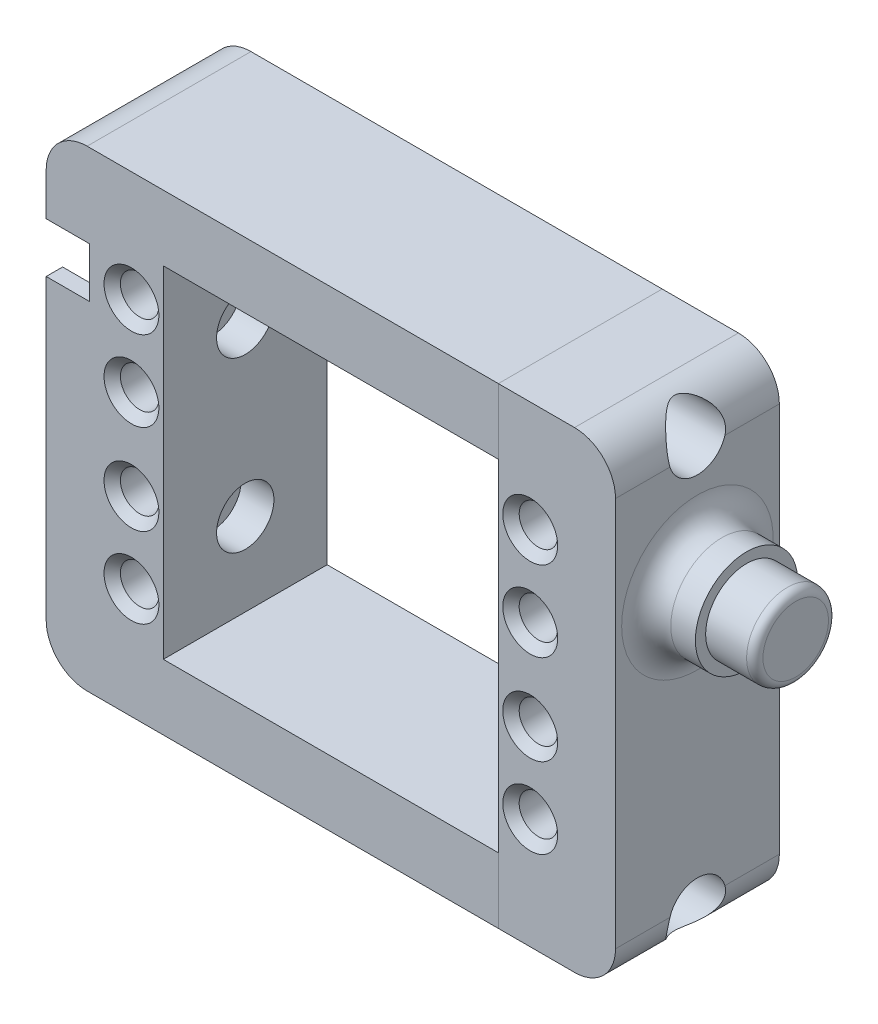
SolidWorks part; units mm, degrees
material "ABS"
ref_plane "Front Plane" through (0, 0, 0) normal (0, 0, 1) x (1, 0, 0)
ref_plane "Top Plane" through (0, 0, 0) normal (0, 1, 0) x (1, 0, 0)
ref_plane "Right Plane" through (0, 0, 0) normal (1, 0, 0) x (0, 0, -1)
sketch "Sketch1" plane through (0, 0, 0) normal (1, 0, 0) x (0, 0, -1)
  line L1 (-10, 10) -> (10, 10)
  line L2 (-10, 10) -> (-10, -10)
  line L3 (-10, -10) -> (10, -10)
  line L4 (10, 10) -> (10, -10)
  line L5 (-10, 10) -> (10, -10) construction
  line L6 (-10, -10) -> (10, 10) construction
  point P0 (0, 0)
  dimension "D1" = 20
  dimension "D2" = 20
extrude "Boss-Extrude1" add sketch "Sketch1" along normal blind 20
sketch "Sketch2" plane through (20, 0, 0) normal (1, 0, 0) x (0, 0, -1)
  line L1 (-10, 35) -> (10, 35)
  line L2 (-10, 35) -> (-10, -35)
  line L3 (-10, -35) -> (10, -35)
  line L4 (10, 35) -> (10, -35)
  line L5 (-10, 35) -> (10, -35) construction
  line L6 (-10, -35) -> (10, 35) construction
  point P0 (0, 0)
  dimension "D1" = 20
  dimension "D2" = 70
extrude "Boss-Extrude2" add sketch "Sketch2" along normal blind 10.3
sketch "Sketch4" plane through (30.3, 0, 0) normal (1, 0, 0) x (0, 0, -1)
  line L0 (0, 7.65) -> (0, 8.1702) construction
  line L1 (7.65, 7.65) -> (-7.65, 7.65) construction
  line L17 (4.15, -26.55) -> (-4.15, -26.55) construction
  line L18 (-7.65, 7.65) -> (7.65, 7.65) construction
  line L22 (-7.65, 7.65) -> (-7.65, -27.55) construction
  line L23 (-7.65, -27.55) -> (7.65, -27.55) construction
  line L24 (7.65, 7.65) -> (7.65, -27.55) construction
  line L25 (-7.65, 7.65) -> (7.65, -27.55) construction
  line L26 (-7.65, -27.55) -> (7.65, 7.65) construction
  line L27 (4.15, -26.55) -> (4.15, -28.55) construction
  line L28 (4.15, -28.55) -> (-4.15, -28.55) construction
  line L29 (-4.15, -26.55) -> (-4.15, -28.55) construction
  line L30 (4.15, -26.55) -> (-4.15, -28.55) construction
  line L31 (4.15, -28.55) -> (-4.15, -26.55) construction
  line L34 (4.15, -28.55) -> (-4.15, -28.55)
  line L35 (-4.15, -28.55) -> (-4.15, -7.3118)
  line L36 (4.15, -28.55) -> (4.15, -7.3118)
  arc A1 (4.15, -6.4265) -> (-4.15, -6.4265) centre (0, 0) ccw construction
  arc A2 (4.15, -7.3118) -> (-4.15, -7.3118) centre (0, 0) ccw
  point P1 (0, -27.55)
  point P7 (0, -13.75)
  point P10 (0, 7.65)
  point P14 (0, -9.95)
  dimension "D1" = 15.3
  dimension "D5" = 2
  dimension "D2" = 15.3
  dimension "D3" = 35.2
  dimension "D4" = 8.3
extrude "Cut-Extrude1" cut sketch "Sketch4" against normal blind 5.8
fillet "Fillet1" radius 4.15 2 edges at (27.4, -28.55, 4.15) (27.4, -28.55, -4.15)
fillet "Fillet2" radius 10 2 edges at (27.4, -7.3118, 4.15) (27.4, -7.3118, -4.15)
sketch "Sketch5" plane through (0, 0, 0) normal (-1, 0, 0) x (0, 0, 1)
  circle A0 centre (0, 0) radius 1.75
  dimension "D1" = 3.5
extrude "Cut-Extrude2" cut sketch "Sketch5" against normal through all
sketch "Sketch6" plane through (24.5, 0, 0) normal (1, 0, 0) x (0, 0, -1)
  line L0 (0, -19.35) -> (0, 0) construction
  line L1 (0, -25.65) -> (0, -23.15) construction
  line L2 (0, -23.15) -> (0, -21.85) construction
  line L3 (0, -21.85) -> (0, -19.35) construction
  line L5 (0, 0) -> (1.164, 0) construction
  line L6 (0, 0) -> (0, -9.35) construction
  line L7 (0, -9.35) -> (1.164, -9.35) construction
  line L8 (1.164, 0) -> (1.164, -9.35) construction
  line L9 (0, 0) -> (1.164, -9.35) construction
  line L10 (0, -9.35) -> (1.164, 0) construction
  circle A0 centre (0, -20.6) radius 1.75
  circle A1 centre (0, -9.35) radius 1.75 construction
  point P11 (0.582, -4.675)
  dimension "D5" = 3.5
  dimension "D6" = 9.35
  dimension "D7" = 3.5
  dimension "D1" = 19.35
  dimension "D2" = 2.5
  dimension "D3" = 1.3
  dimension "D4" = 2.5
extrude "Cut-Extrude3" cut sketch "Sketch6" against normal up to next
sketch "Sketch13" plane through (0, 0, 0) normal (-1, 0, 0) x (0, 0, 1)
  line L1 (-10, 10) -> (10, 10)
  line L2 (-10, 10) -> (-10, -10)
  line L3 (-10, -10) -> (10, -10)
  line L4 (10, 10) -> (10, -10)
extrude "Cut-Extrude9" cut sketch "Sketch13" against normal up to surface (20 mm away) up to face at (20, 22.5, 0)
sketch "Sketch29" plane through (30.3, 0, 0) normal (1, 0, 0) x (0, 0, -1)
  line L0 (0, 0) -> (0, 2.6) construction
  line L1 (15.1094, -8.7) -> (15.1094, -2.6)
  line L2 (0, 2.6) -> (-15.1094, 2.6)
  line L4 (0, 2.6) -> (0, 3.8)
  line L5 (0, 3.8) -> (0, 7.5)
  line L6 (0, 7.5) -> (0, 8.7)
  line L7 (0, 8.7) -> (-15.1094, 8.7)
  line L8 (-15.1094, 8.7) -> (-15.1094, 2.6)
  line L9 (0, -2.6) -> (15.1094, -2.6)
  line L10 (0, -2.6) -> (0, -3.8)
  line L11 (0, -3.8) -> (0, -7.5)
  line L12 (0, -7.5) -> (0, -8.7)
  line L13 (0, -8.7) -> (15.1094, -8.7)
  point P19 (0, 0)
  dimension "D1" = 2.6
  dimension "D2" = 1.2
  dimension "D3" = 3.7
  dimension "D4" = 1.2
  dimension "D5" = 2
extrude "Cut-Extrude18" cut sketch "Sketch29" against normal blind 5.3
sketch "Sketch32" plane through (30.3, 0, 0) normal (1, 0, 0) x (0, 0, -1)
  line L0 (0, -28.55) -> (0, -38.725) construction
  line L1 (10, -35) -> (10, -8.7) construction
  line L2 (-10, -35) -> (10, -35)
  line L3 (-10, -35) -> (-10, -38.725)
  line L4 (-10, -38.725) -> (10, -38.725)
  line L5 (10, -35) -> (10, -38.725)
  dimension "D1" = 10.175
extrude "Boss-Extrude3" add sketch "Sketch32" against normal up to surface (10.3 mm away) up to face at (20, 0, 0)
sketch "Sketch31" plane through (30.3, 0, 0) normal (1, 0, 0) x (0, 0, -1)
  line L2 (0, 8.7) -> (0, 18.875) construction
  line L3 (10, -2.6) -> (10, 35) construction
  line L4 (-10, 35) -> (10, 35)
  line L5 (-10, 35) -> (-10, 18.875)
  line L6 (-10, 18.875) -> (10, 18.875)
  line L7 (10, 35) -> (10, 18.875)
  dimension "D1" = 10.175
extrude "Cut-Extrude19" cut sketch "Sketch31" against normal through all
sketch "Sketch34" plane through (20, 0, 0) normal (-1, 0, 0) x (0, 0, 1)
  line L4 (10, -38.725) -> (10, 18.875)
  line L5 (10, 18.875) -> (-10, 18.875)
  line L6 (-10, 18.875) -> (-10, -38.725)
  line L7 (-10, -38.725) -> (10, -38.725)
  line L8 (10, -38.725) -> (10, 18.875)
  line L9 (10, 18.875) -> (-10, 18.875)
  line L10 (-10, 18.875) -> (-10, -38.725)
  line L11 (-10, -38.725) -> (10, -38.725)
  circle A0 centre (0, -20.6) radius 1.75 construction
  circle A1 centre (0, 0) radius 1.75 construction
  circle A2 centre (0, -20.6) radius 1.75
  circle A3 centre (0, 0) radius 1.75
  dimension "D1" = 0
extrude "Boss-Extrude5" add sketch "Sketch34" along normal blind 4
sketch "Sketch35" plane through (16, 0, 0) normal (-1, 0, 0) x (0, 0, 1)
  line L0 (10, -38.725) -> (10, 18.875) construction
  line L1 (-10, 18.875) -> (10, 18.875)
  line L2 (-10, 18.875) -> (-10, 10.875)
  line L3 (-10, 10.875) -> (10, 10.875)
  line L4 (10, 18.875) -> (10, 10.875)
  line L5 (0, 10.875) -> (0, -30.725) construction
  line L6 (-10, -38.725) -> (10, -38.725)
  line L7 (-10, -38.725) -> (-10, -30.725)
  line L8 (-10, -30.725) -> (10, -30.725)
  line L9 (10, -38.725) -> (10, -30.725)
  dimension "D1" = 41.6
extrude "Boss-Extrude6" add sketch "Sketch35" along normal blind 40.9
sketch "Sketch37" plane through (-24.9, 0, 0) normal (-1, 0, 0) x (0, 0, 1)
  line L1 (-10, 18.875) -> (10, 18.875)
  line L2 (-10, 18.875) -> (-10, -38.725)
  line L3 (-10, -38.725) -> (10, -38.725)
  line L4 (10, 18.875) -> (10, -38.725)
extrude "Boss-Extrude7" add sketch "Sketch37" along normal blind 14.3
sketch "Sketch38" plane through (0, 0, 10) normal (0, 0, 1) x (1, 0, 0)
  line L0 (-24.9, 10.875) -> (-24.9, -9.925) construction
  line L1 (-24.9, -9.925) -> (-24.9, -30.725) construction
  line L2 (-24.9, -30.725) -> (-24.9, 10.875) construction
  line L3 (-24.9, -9.925) -> (-39.2, -9.925) construction
  line L4 (-39.2, -38.725) -> (-39.2, 18.875) construction
  line L5 (-24.9, 0.475) -> (-28.79, 0.475) construction
  line L6 (-28.79, 0.475) -> (-28.79, 5.375) construction
  line L7 (-24.9, 10.875) -> (16, 10.875) construction
  line L8 (-4.45, 10.875) -> (-4.45, -38.725) construction
  line L9 (-39.2, -38.725) -> (30.3, -38.725) construction
  circle A0 centre (-28.79, 5.375) radius 2.35
  circle A1 centre (-28.79, -4.425) radius 2.35
  circle A2 centre (-28.79, -25.225) radius 2.35
  circle A3 centre (-28.79, -15.425) radius 2.35
  circle A4 centre (19.89, 5.375) radius 2.35
  circle A5 centre (19.89, -4.425) radius 2.35
  circle A6 centre (19.89, -15.425) radius 2.35
  circle A7 centre (19.89, -25.225) radius 2.35
  dimension "D4" = 4.7
  dimension "D1" = 41.6
  dimension "D2" = 3.89
  dimension "D3" = 4.9
extrude "Cut-Extrude20" cut sketch "Sketch38" against normal blind 8
chamfer "Chamfer1" distance 1 angle 45 8 edges at (22.24, -25.225, 10) (17.54, -15.425, 10) (22.24, -4.425, 10) (17.54, 5.375, 10) (-26.44, 5.375, 10) (-26.44, -15.425, 10) (-31.14, -25.225, 10) (-31.14, -4.425, 10)
sketch "Sketch41" plane through (16, 0, 0) normal (-1, 0, 0) x (0, 0, 1)
  circle A0 centre (0, 0) radius 3.5
  circle A1 centre (0, -20.6) radius 3.5
  dimension "D1" = 7
  dimension "D2" = 7
extrude "Cut-Extrude23" cut sketch "Sketch41" against normal blind 4
sketch "Sketch42" plane through (-39.2, 0, 0) normal (-1, 0, 0) x (0, 0, 1)
  line L0 (10, -38.725) -> (10, 18.875) construction
  line L1 (-10, -38.725) -> (10, -38.725) construction
  line L2 (-10, -38.725) -> (-10, -30.725) construction
  line L3 (-10, -30.725) -> (10, -30.725) construction
  line L4 (10, -38.725) -> (10, -30.725) construction
  line L5 (-10, -9.925) -> (10, -9.925) construction
  line L6 (-10, 18.875) -> (-10, -38.725) construction
  circle A0 centre (0, -34.725) radius 1.75
  circle A1 centre (0, 14.875) radius 1.75
  point P9 (-10, -34.725)
  dimension "D2" = 3.5
  dimension "D1" = 8
  dimension "D3" = 4
  dimension "D4" = 10
extrude "Cut-Extrude24" cut sketch "Sketch42" against normal blind 22.3
sketch "Sketch43" plane through (-39.2, 0, 0) normal (-1, 0, 0) x (0, 0, 1)
  circle A0 centre (0, 14.875) radius 3.5
  circle A1 centre (0, -34.725) radius 3.5
  dimension "D1" = 7
  dimension "D2" = 7
extrude "Cut-Extrude25" cut sketch "Sketch43" against normal blind 11
fillet "Fillet3" radius 5 4 edges at (-39.2, -38.725, 0) (30.3, -38.725, 0) (30.3, 18.875, 0) (-39.2, 18.875, 0)
sketch "Sketch44" plane through (0, 0, 10) normal (0, 0, 1) x (1, 0, 0)
  line L0 (-24.9, 18.875) -> (-24.9, -38.725)
  line L1 (-34.2, 18.875) -> (25.3, 18.875) construction
  line L2 (-34.2, -38.725) -> (25.3, -38.725) construction
split "Split1" trim tools "Sketch44" bodies to split 171 resulting bodies 172 173
sketch "Sketch45" plane through (-24.9, 0, 0) normal (-1, 0, 0) x (0, 0, 1)
  circle A0 centre (0, 14.875) radius 2.35
  circle A1 centre (0, -34.725) radius 2.35
  dimension "D1" = 4.7
  dimension "D2" = 4.7
extrude "Cut-Extrude26" cut sketch "Sketch45" against normal blind 8
chamfer "Chamfer2" distance 1 angle 45 2 edges at (-24.9, -34.725, 2.35) (-24.9, 14.875, 2.35)
sketch "Sketch46" plane through (-39.2, 0, 0) normal (-1, 0, 0) x (0, 0, 1)
  circle A1 centre (0, 0) radius 5
  dimension "D1" = 10
extrude "Boss-Extrude8" add sketch "Sketch46" along normal blind 12
fillet "Fillet5" radius 1 1 edges at (-51.2, 0, 5)
sketch "Sketch50" plane through (-39.2, 0, 0) normal (-1, 0, 0) x (0, 0, 1)
  circle A0 centre (0, 0) radius 6.25
  dimension "D1" = 12.5
extrude "Boss-Extrude9" add sketch "Sketch50" along normal blind 6
fillet "Fillet6" radius 3 1 edges at (-39.2, 0, 6.25)
mirror "Mirror1" about plane through (-39.2, 0, 0) normal (-1, 0, 0) of bodies 178 174 167 172 173
delete or keep bodies "Body-Delete/Keep 1" type delete bodies bodies 178 174
sketch "Sketch47" [suppressed] plane through (0, 0, 10) normal (0, 0, 1) x (1, 0, 0)
  line L0 (19.89, 5.375) -> (19.89, -4.425)
  line L1 (19.89, 0.475) -> (28.8988, 0.475)
sketch "Sketch48" [suppressed] plane through (24.5, 0, 0) normal (1, 0, 0) x (0, 0, -1)
  line L0 (0, 0) -> (-13.129, 0)
  line L1 (-10, 8.725) -> (-10, 2.025) construction
sketch "Sketch49" [suppressed] plane through (0, 0, 10) normal (0, 0, 1) x (1, 0, 0)
  line L0 (24.5491, 0) -> (24.5491, 0.475)
  line L1 (19.89, 0.475) -> (28.8988, 0.475) construction
